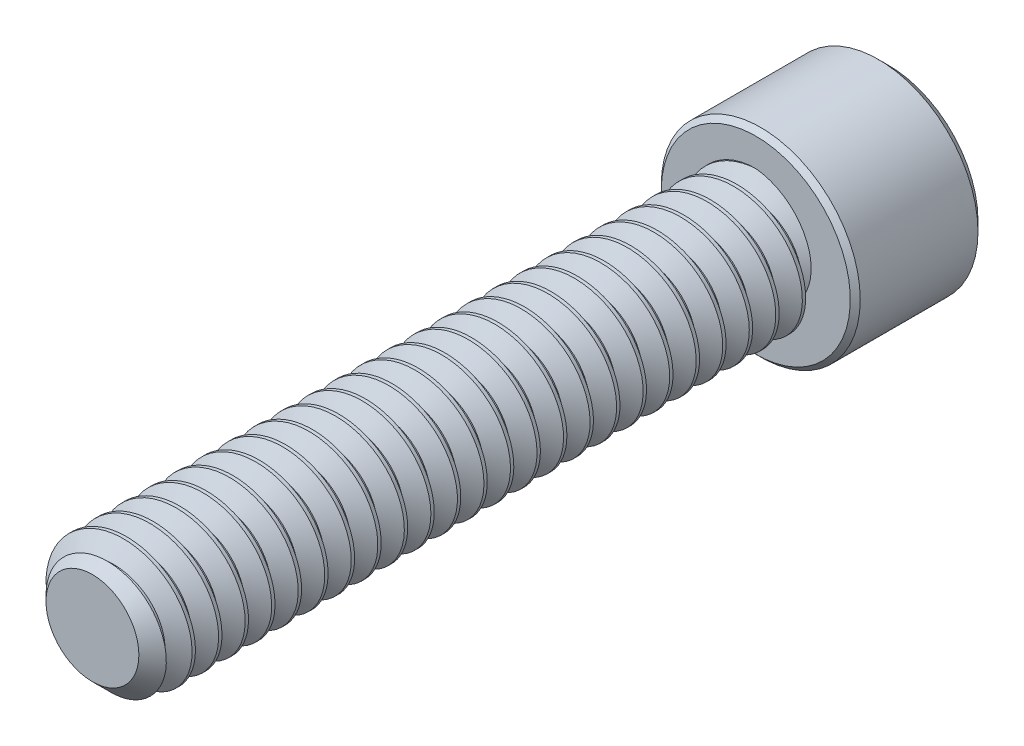
SolidWorks part; units mm, degrees
ref_plane "Front Plane" through (0, 0, 0) normal (0, 0, 1) x (1, 0, 0)
ref_plane "Top Plane" through (0, 0, 0) normal (0, 1, 0) x (1, 0, 0)
ref_plane "Right Plane" through (0, 0, 0) normal (1, 0, 0) x (0, 0, -1)
sketch "Sketch0" plane through (0, 0, 0) normal (1, 0, 0) x (0, 0, -1)
  line L0 (0, 0) -> (31.75, 0) construction
  point P2 (38.1, 0)
  point P4 (0, 0)
  dimension "D1" = 31.75
  dimension "D2" = 6.35
  dimension "Min Thread" = 0
sketch "Sketch1" plane through (0, 0, 0) normal (0, 0, 1) x (1, 0, 0)
  circle A0 centre (0, 0) radius 3.175
  dimension "OD" = 6.35
extrude "Extrude1" add sketch "Sketch1" against normal blind 31.75
sketch "Sketch2" plane through (0, 0, 0) normal (0, 0, 1) x (1, 0, 0)
  circle A0 centre (0, 0) radius 3.175 construction
  circle A1 centre (0, 0) radius 3.175
curve "Helix/Spiral1" pitch 1.27 height 33.02 turns 26 parameters "pitch"=1.27
chamfer "Chamfer3" distance 0.9525 angle 45 1 edges at (3.175, 0, 0)
sketch "Sketch3" plane through (0, 0, 0) normal (1, 0, 0) x (0, 0, -1)
  line L0 (-1.1113, 3.175) -> (-0.635, 2.3501)
  line L1 (-0.635, 2.3501) -> (-0.4763, 2.3501)
  line L2 (-0.4763, 2.3501) -> (0, 3.175)
  line L3 (-1.1113, 3.175) -> (0, 3.175)
  line L4 (-0.5556, 3.175) -> (-0.5556, 2.3501) construction
  line L5 (-0.8731, 2.7626) -> (-0.2381, 2.7626) construction
  line L6 (0, 3.175) -> (0, -3.175) construction
  dimension "D1" = 0.1588
  dimension "D2" = 0.635
  dimension "D3" = 60
sweep "Cut-Sweep1" cut profiles "Sketch3" path "Helix/Spiral1"
sketch "Sketch5" plane through (0, 0, 0) normal (1, 0, 0) x (0, 0, -1)
  line L0 (31.75, -2.3728) -> (31.75, 2.2654) construction
  line L1 (31.75, 3.175) -> (0, 3.175)
  line L2 (31.75, 3.175) -> (31.75, 0)
  line L3 (31.75, 0) -> (-1.1556, 0)
  line L4 (0, 0) -> (31.75, 0) construction
  line L5 (0, 3.175) -> (-1.1556, 0)
  line L6 (0, 0) -> (34.29, 0) construction
  dimension "D1" = 70
  dimension "D3" = 2.54
revolve "partially thread" [suppressed] add sketch "Sketch5" angle 360 about L6
sketch "Sketch6" plane through (0, 0, -31.75) normal (0, 0, -1) x (-1, 0, 0)
  circle A0 centre (0, 0) radius 4.7625
  dimension "head dia" = 9.525
extrude "Extrude2" add sketch "Sketch6" along normal blind 6.35
sketch "Sketch7" plane through (0, 0, -38.1) normal (0, 0, -1) x (-1, 0, 0)
  line L1 (0, 2.7496) -> (-2.3813, 1.3748)
  line L2 (-2.3813, 1.3748) -> (-2.3813, -1.3748)
  line L3 (-2.3813, -1.3748) -> (0, -2.7496)
  line L4 (0, -2.7496) -> (2.3813, -1.3748)
  line L5 (2.3813, -1.3748) -> (2.3813, 1.3748)
  line L6 (2.3813, 1.3748) -> (0, 2.7496)
  circle A0 centre (0, 0) radius 2.3813 construction
  dimension "hex dia" = 4.7625
extrude "Cut-Extrude1" cut sketch "Sketch7" against normal blind 3.5719
sketch "Sketch8" plane through (0, 0, -38.1) normal (0, 0, -1) x (-1, 0, 0)
  circle A0 centre (0, 0) radius 2.7496
extrude "Cut-Extrude2" cut sketch "Sketch8" against normal through all draft 45
chamfer "Chamfer1" distance 0.4763 angle 45 1 edges at (-4.7625, 0, -38.1)
chamfer "Chamfer2" distance 0.2381 angle 45 1 edges at (-4.7625, 0, -31.75)
sketch "Sketch9" plane through (0, 0, 0) normal (1, 0, 0) x (0, 0, -1)
  line L0 (0, 3.175) -> (0, -3.175) construction
  line L1 (3.175, 3.175) -> (3.175, -3.175) construction
  line L2 (38.1, 4.7625) -> (38.1, -4.7625) construction
  line L3 (31.75, 4.7625) -> (31.75, -4.7625) construction
  line L4 (31.75, 4.5244) -> (31.75, -4.5244) construction
  line L5 (38.1, -4.2863) -> (38.1, 4.2863) construction
  line L6 (31.75, -4.7625) -> (31.75, 4.7625) construction
  line L7 (0, 2.2225) -> (0, -2.2225) construction
  line L8 (-1.1113, 3.175) -> (0, 3.175) construction
  line L9 (3.175, 0) -> (0, 0) construction
  dimension "D1" = 3.175
equation "\"D3@Helix/Spiral1\" = \"screw length@Extrude1\"+\"pitch@Helix/Spiral1\""
equation "\"D1@Sketch3\" = \"pitch@Helix/Spiral1\"*.125"
equation "\"D2@Sketch3\" = \"pitch@Helix/Spiral1\"*.5"
equation "\"D1@Cut-Extrude1\" = \"hex dia@Sketch7\"*.75"
equation "\"D1@Chamfer1\" = \"head dia@Sketch6\"*.05"
equation "\"D1@Sketch9\" = \"pitch@Helix/Spiral1\"*2.50"
equation "\"D1@Chamfer2\" = \"D1@Chamfer1\"/2"
equation "\"D1@Chamfer3\" = \"pitch@Helix/Spiral1\"*.750"
equation "\"D1@Sketch0\" = \"screw length@Extrude1\""
equation "\"D2@Sketch0\" = \"head depth@Extrude2\""
